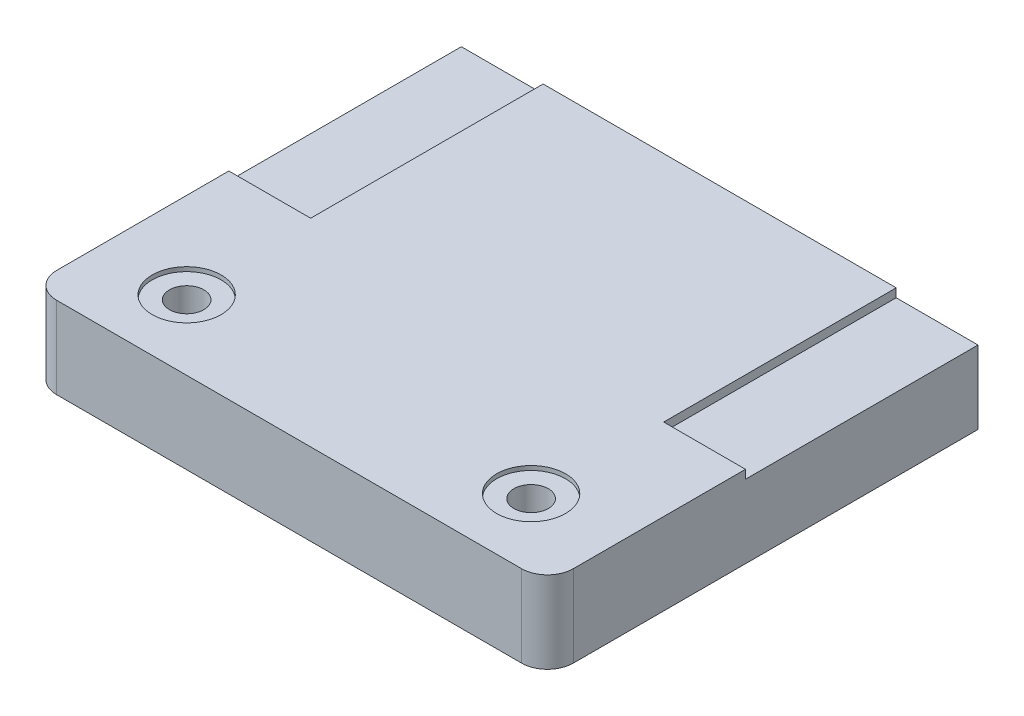
SolidWorks part; units mm, degrees
ref_plane "前视基准面" through (0, 0, 0) normal (0, 0, 1) x (1, 0, 0)
ref_plane "上视基准面" through (0, 0, 0) normal (0, 1, 0) x (1, 0, 0)
ref_plane "右视基准面" through (0, 0, 0) normal (1, 0, 0) x (0, 0, -1)
sketch "草图1" plane through (0, 0, 0) normal (0, 1, 0) x (1, 0, 0)
  line L1 (-30, 25) -> (30, 25)
  line L2 (-30, 25) -> (-30, -25)
  line L3 (-30, -25) -> (30, -25)
  line L4 (30, 25) -> (30, -25)
  line L5 (-30, 25) -> (30, -25) construction
  line L6 (-30, -25) -> (30, 25) construction
  point P0 (0, 0)
  dimension "D1" = 60
  dimension "D2" = 50
extrude "凸台-拉伸1" add sketch "草图1" along normal blind 9.5
fillet "圆角1" radius 3 2 edges at (-30, 4.75, 25) (30, 4.75, 25)
sketch "草图2" plane through (0, 9.5, 0) normal (0, 1, 0) x (1, 0, 0)
  line L0 (0, 0) -> (0, -25) construction
  line L1 (-27, -25) -> (27, -25) construction
  circle A0 centre (-20, -16.9) radius 4
  circle A1 centre (20, -16.9) radius 4
  dimension "D1" = 8
  dimension "D2" = 40
  dimension "D3" = 8.1
extrude "切除-拉伸1" cut sketch "草图2" against normal blind 0.5 contours A1 | A0
sketch "草图4" plane through (0, 9.5, 0) normal (0, 1, 0) x (1, 0, 0)
  line L1 (-20.5, -2) -> (-30, -2)
  line L2 (-20.5, -2) -> (-20.5, 25)
  line L3 (-20.5, 25) -> (-30, 25)
  line L4 (-30, -2) -> (-30, 25)
  line L5 (20.5, -2) -> (30, -2)
  line L6 (20.5, -2) -> (20.5, 25)
  line L7 (20.5, 25) -> (30, 25)
  line L8 (30, -2) -> (30, 25)
extrude "切除-拉伸2" cut sketch "草图4" against normal blind 1
sketch "草图5" plane through (0, 9.5, 0) normal (0, 1, 0) x (1, 0, 0)
  circle A0 centre (-20, -16.9) radius 2
  circle A1 centre (20, -16.9) radius 2
  dimension "D1" = 4
extrude "切除-拉伸3" cut sketch "草图5" against normal through all
